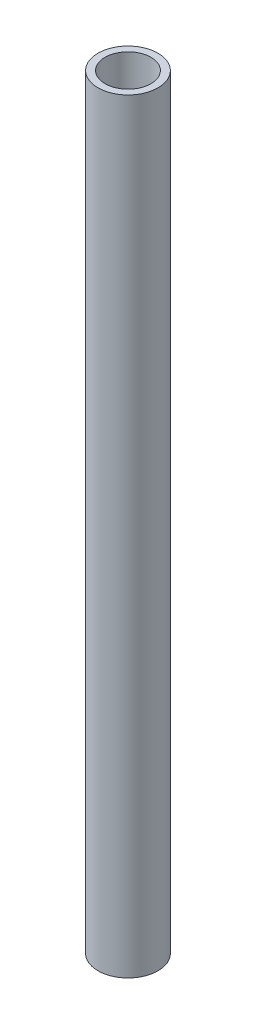
SolidWorks part; units mm, degrees
material "AISI 304"
ref_plane "Front Plane" through (0, 0, 0) normal (0, 0, 1) x (1, 0, 0)
ref_plane "Top Plane" through (0, 0, 0) normal (0, 1, 0) x (1, 0, 0)
ref_plane "Right Plane" through (0, 0, 0) normal (1, 0, 0) x (0, 0, -1)
ref_axis "Axial" through (0, 55, 0) along (0, -1, 0)
ref_plane "Bottom Plane" through (0, -12.065, 0) normal (0, 1, 0) x (1, 0, 0)
sketch "Sketch1" plane through (0, 0, 0) normal (0, 1, 0) x (1, 0, 0)
  circle A0 centre (0, 0) radius 0.4953
  circle A1 centre (0, 0) radius 0.6477
  dimension "D1" = 0.9906
  dimension "D2" = 1.2954
extrude "Needle" add sketch "Sketch1" against normal blind 16.51
